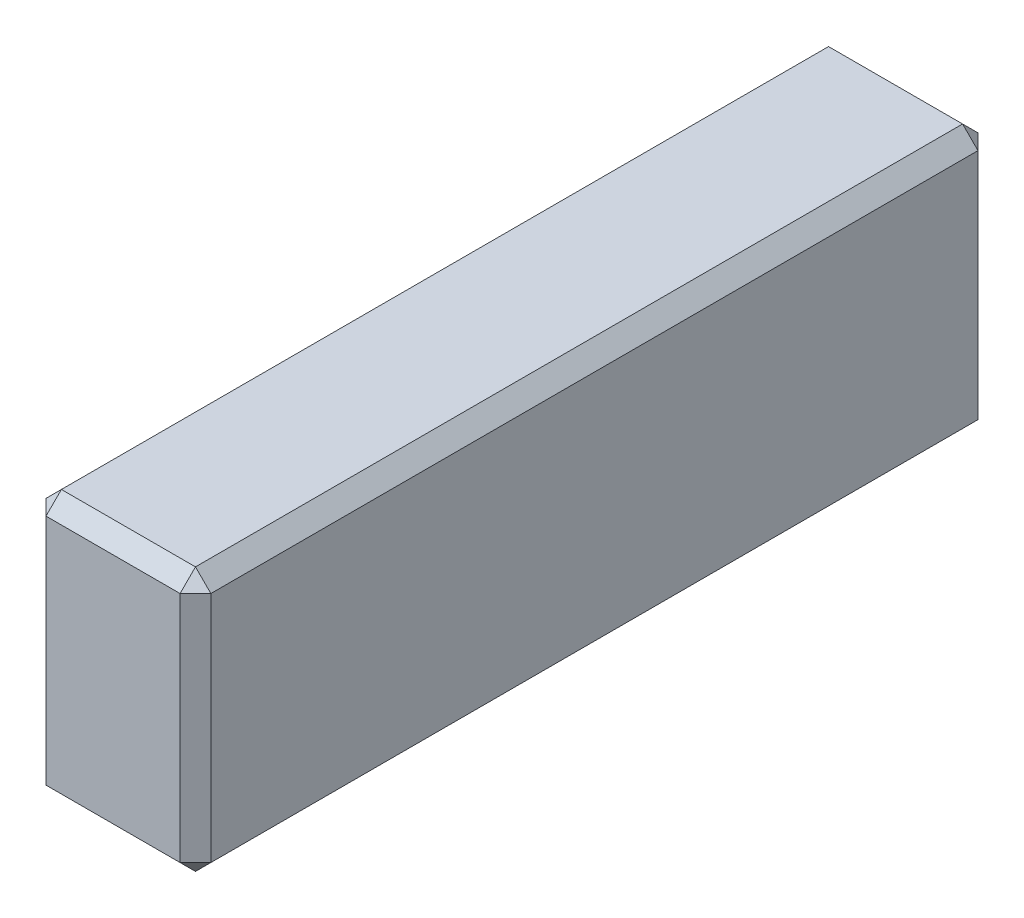
SolidWorks part; units mm, degrees
material "Polyurethane Foam Rigid"
ref_plane "Front Plane" through (0, 0, 0) normal (0, 0, 1) x (1, 0, 0)
ref_plane "Top Plane" through (0, 0, 0) normal (0, 1, 0) x (1, 0, 0)
ref_plane "Right Plane" through (0, 0, 0) normal (1, 0, 0) x (0, 0, -1)
sketch "Sketch1" plane through (0, 0, 0) normal (0, 0, 1) x (1, 0, 0)
  line L0 (-37.5, 60) -> (-37.5, -60)
  line L1 (-37.5, 60) -> (37.5, 60)
  line L2 (-37.5, -60) -> (37.5, -60)
  line L3 (37.5, 60) -> (37.5, -60)
  line L4 (-37.5, 60) -> (37.5, -60) construction
  line L5 (-37.5, -60) -> (37.5, 60) construction
  point P1 (0, 0)
  dimension "D1" = 75
  dimension "D2" = 120
extrude "Boss-Extrude1" add sketch "Sketch1" along normal mid plane 363
sketch "Sketch2" plane through (-37.5, 0, 131.5) normal (1, 0, 0) x (0, 0, -1)
  line L0 (143.5, -60) -> (143.5, -10)
  line L1 (143.5, -60) -> (119.5, -60)
  line L2 (143.5, -10) -> (119.5, -10)
  line L3 (119.5, -60) -> (119.5, -10)
  line L4 (143.5, -60) -> (119.5, -10) construction
  line L5 (143.5, -10) -> (119.5, -60) construction
  line L7 (-50, -60) -> (313, -60) construction
  point P0 (131.5, -60)
  point P1 (131.5, -35)
  dimension "D2" = 50
  dimension "D3" = 24
extrude "Cut-Extrude1" cut sketch "Sketch2" along normal blind 15
shell "Shell1" thickness 13
sketch "Sketch3" plane through (0, 0, 0) normal (0, 0, 1) x (1, 0, 0)
  line L0 (-22.5, 6.5) -> (22.5, 6.5)
  line L1 (-22.5, 6.5) -> (-22.5, -6.5)
  line L2 (22.5, 6.5) -> (22.5, -6.5)
  line L3 (-22.5, -6.5) -> (22.5, -6.5)
  line L4 (-22.5, 6.5) -> (22.5, -6.5) construction
  line L5 (22.5, 6.5) -> (-22.5, -6.5) construction
  line L6 (0, 60) -> (0, 47) construction
  line L7 (37.5, 60) -> (-37.5, 60) construction
  line L8 (24.5, 47) -> (-24.5, 47) construction
  line L10 (-22.5, -10) -> (-22.5, -47) construction
  point P1 (0, 0)
extrude "Boss-Extrude2" add sketch "Sketch3" against normal up to body and the other way up to body
chamfer "Chamfer1" distance 7 angle 45 11 edges at (0, -60, 181.5) (37.5, 0, 181.5) (0, 60, 181.5) (37.5, 0, -181.5) (0, -60, -181.5) (-37.5, 0, -181.5) (0, 60, -181.5) (-37.5, 0, 181.5) (37.5, 60, 0) (37.5, -60, 0) (-37.5, 60, 0)
sketch "Sketch4" plane through (-37.5, 0, 0) normal (-1, 0, 0) x (0, 0, 1)
  line L4 (-12, -10) -> (-12, -60)
  line L5 (12, -10) -> (-12, -10)
  line L6 (12, -60) -> (12, -10)
  line L7 (-12, -60) -> (12, -60)
  line L8 (-12, 31.5245) -> (-12, -72.5036)
  line L9 (12, 31.5245) -> (-12, 31.5245)
  line L10 (12, -72.5036) -> (12, 31.5245)
  line L11 (-12, -72.5036) -> (12, -72.5036)
  dimension "D1" = 0
extrude "Cut-Extrude2" cut sketch "Sketch4" against normal up to surface (49 mm away) from offset 13
